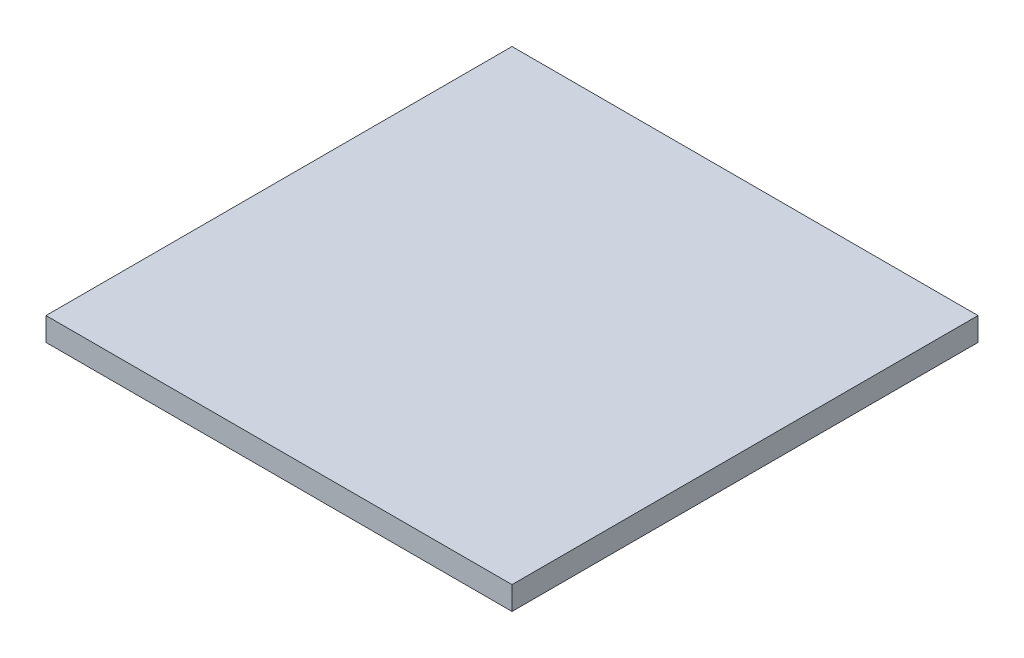
SolidWorks part; units mm, degrees
note: The reader was unsure of these and kept them because the rebuilt part matched: shared geometry of "Sketch1<2>".
ref_plane "Front Plane" through (0, 0, 0) normal (0, 0, 1) x (1, 0, 0)
ref_plane "Top Plane" through (0, 0, 0) normal (0, 1, 0) x (1, 0, 0)
ref_plane "Right Plane" through (0, 0, 0) normal (1, 0, 0) x (0, 0, -1)
sketch "Sketch1" plane through (0, 0, 0) normal (0, 0, 1) x (1, 0, 0)
  line L1 (-200, 5) -> (0, 5)
  line L2 (-200, 5) -> (-200, -5)
  line L3 (-200, -5) -> (0, -5)
  line L4 (0, 5) -> (0, -5)
  dimension "D1" = 200
  dimension "D2" = 10
extrude "Boss-Extrude1" add sketch "Sketch1" along normal mid plane 200
surface "Surface-Fill1" sketch "Sketch1<2>"
sketch "Sketch1<2>" plane through (0, 0, 0) normal (0, 0, 1) x (1, 0, 0) same geometry as "Sketch1"
